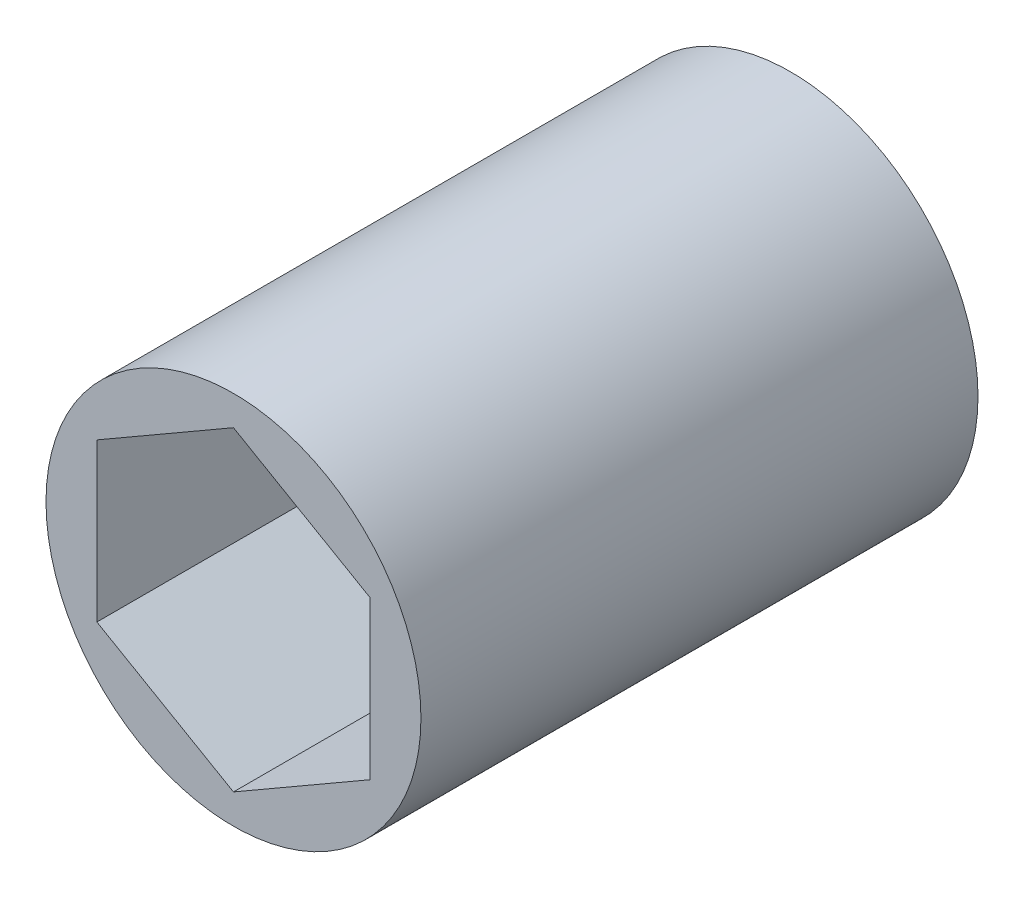
SolidWorks part; units mm, degrees
material "6061-T6 (SS)"
ref_plane "Front" through (0, 0, 0) normal (0, 0, 1) x (1, 0, 0)
ref_plane "Top" through (0, 0, 0) normal (0, 1, 0) x (1, 0, 0)
ref_plane "Right" through (0, 0, 0) normal (1, 0, 0) x (0, 0, -1)
sketch "Sketch1" plane through (0, 0, 0) normal (0, 0, 1) x (1, 0, 0)
  line L1 (0, 7.479) -> (-6.477, 3.7395)
  line L2 (-6.477, 3.7395) -> (-6.477, -3.7395)
  line L3 (-6.477, -3.7395) -> (0, -7.479)
  line L4 (0, -7.479) -> (6.477, -3.7395)
  line L5 (6.477, -3.7395) -> (6.477, 3.7395)
  line L6 (6.477, 3.7395) -> (0, 7.479)
  circle A0 centre (0, 0) radius 8.89
  circle A1 centre (0, 0) radius 6.477 construction
  dimension "D2" = 17.78
  dimension "D1" = 12.954
extrude "Boss-Extrude1" add sketch "Sketch1" along normal blind 26.416
